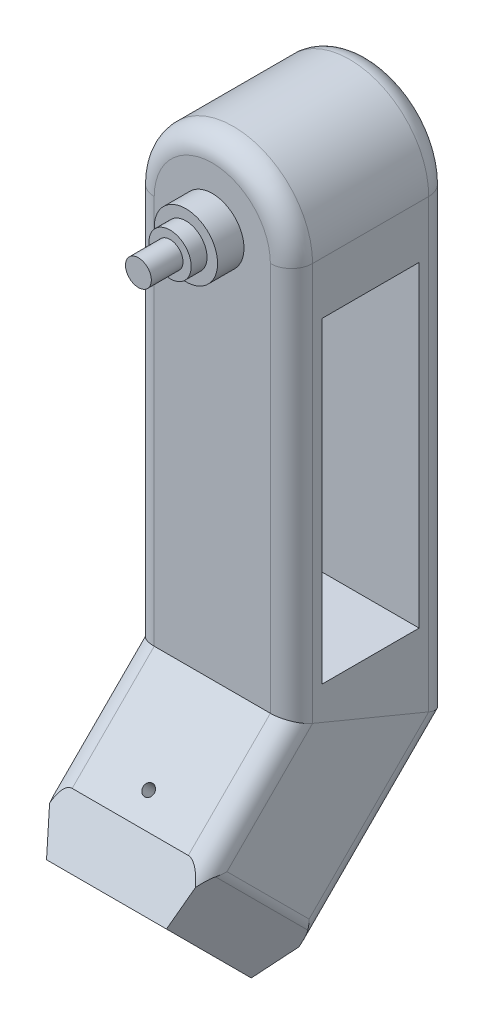
SolidWorks part; units mm, degrees
ref_plane "Front Plane" through (0, 0, 0) normal (0, 0, 1) x (1, 0, 0)
ref_plane "Top Plane" through (0, 0, 0) normal (0, 1, 0) x (1, 0, 0)
ref_plane "Right Plane" through (0, 0, 0) normal (1, 0, 0) x (0, 0, -1)
ref_plane "Plane2" through (0, 96.393, 0) normal (0, 1, 0) x (1, 0, 0)
sketch "Sketch10" plane through (0, 0, 0) normal (1, 0, 0) x (0, 0, -1)
  line L0 (0, 96.393) -> (0, -5.207)
  line L1 (55, 96.393) -> (-55, 96.393) construction
  line L2 (0, -5.207) -> (-25.3243, -30.5313)
  dimension "D1" = 101.6
  dimension "D2" = 35.814
  dimension "D3" = 135
sketch "Sketch11" plane through (0, 96.393, 0) normal (0, 1, 0) x (1, 0, 0)
  line L1 (-19.05, -19.05) -> (19.05, -19.05)
  line L2 (-19.05, -19.05) -> (-19.05, 19.05)
  line L3 (-19.05, 19.05) -> (19.05, 19.05)
  line L4 (19.05, -19.05) -> (19.05, 19.05)
  line L5 (-19.05, -19.05) -> (19.05, 19.05) construction
  line L6 (-19.05, 19.05) -> (19.05, -19.05) construction
  point P0 (0, 0)
  dimension "D1" = 38.1
sweep "Sweep1" add profiles "Sketch11" path "Sketch10"
sketch "Sketch12" plane through (0, -27.9278, 27.9278) normal (0, -0.7071, 0.7071) x (1, 0, 0)
  line L4 (19.05, -22.7319) -> (19.05, 15.3681)
  line L5 (19.05, -22.7319) -> (19.05, 15.3681)
  line L6 (19.05, 15.3681) -> (-19.05, 15.3681)
  line L7 (19.05, 15.3681) -> (-19.05, 15.3681)
  line L8 (-19.05, 15.3681) -> (-19.05, -22.7319)
  line L9 (-19.05, 15.3681) -> (-19.05, -22.7319)
  line L10 (-19.05, -22.7319) -> (19.05, -22.7319)
  line L11 (-19.05, -22.7319) -> (19.05, -22.7319)
  dimension "D1" = 0
extrude "Boss-Extrude5" add sketch "Sketch12" along normal blind 12.7 draft 20
sketch "Sketch13" plane through (0, 0, -19.05) normal (0, 0, -1) x (-1, 0, 0)
  line L0 (20.955, 96.393) -> (-20.955, 96.393) construction
  line L1 (0, 31.8146) -> (0, -31.8146) construction
  line L2 (-19.05, 96.393) -> (19.05, 96.393)
  arc A0 (19.05, 96.393) -> (-19.05, 96.393) centre (0, 96.393) ccw
  dimension "D1" = 38.1
extrude "Boss-Extrude6" add sketch "Sketch13" against normal up to surface (38.1 mm away) up to face at (0, 49.5384, 19.05)
sketch "Sketch15" plane through (0, -36.9081, 36.9081) normal (0, -0.7071, 0.7071) x (1, 0, 0)
  line L1 (-14.4276, 10.7457) -> (14.4276, -18.1095) construction
  line L2 (-14.4276, -18.1095) -> (14.4276, 10.7457) construction
  circle A2 centre (0, -3.6819) radius 12.065
  dimension "D1" = 24.13
extrude "Cut-Extrude3" cut sketch "Sketch15" against normal blind 25.4
sketch "Sketch16" plane through (19.05, 0, 0) normal (1, 0, 0) x (0, 0, -1)
  line L0 (0, 96.393) -> (0, 0) construction
  line L1 (-19.05, 96.393) -> (19.05, 96.393) construction
  line L2 (-19.05, 49.5384) -> (19.05, 49.5384) construction
  line L3 (-19.05, 96.393) -> (-19.05, 2.6838) construction
  line L4 (19.05, 96.393) -> (19.05, -13.0978) construction
  line L5 (-11.6553, 83.82) -> (11.6553, 83.82)
  line L6 (11.6553, 83.82) -> (11.6553, 7.62)
  line L7 (11.6553, 7.62) -> (-11.6553, 7.62)
  line L8 (-11.6553, 7.62) -> (-11.6553, 83.82)
  point P13 (0, 83.82)
  dimension "D1" = 90
  dimension "D2" = 90
  dimension "D3" = 90
  dimension "D4" = 90
  dimension "D5" = 76.2
  dimension "D6" = 23.3106
  dimension "D7" = 23.3106
  dimension "D8" = 83.82
extrude "Cut-Extrude4" cut sketch "Sketch16" against normal blind 59.8307
sketch "Sketch17" plane through (0, 0, 19.05) normal (0, 0, 1) x (1, 0, 0)
  line L0 (0, 115.443) -> (0, 96.393) construction
  line L1 (-19.05, 96.393) -> (19.05, 96.393) construction
  arc A0 (19.05, 96.393) -> (-19.05, 96.393) centre (0, 96.393) ccw construction
  circle A1 centre (0, 96.393) radius 7.62
  dimension "D1" = 15.24
extrude "Boss-Extrude7" add sketch "Sketch17" along normal blind 6.35
sketch "Sketch18" plane through (0, 0, 25.4) normal (0, 0, 1) x (1, 0, 0)
  circle A0 centre (0, 96.393) radius 5.08
  dimension "D1" = 10.16
extrude "Boss-Extrude8" add sketch "Sketch18" along normal blind 3.81
sketch "Sketch19" plane through (0, 0, 29.21) normal (0, 0, 1) x (1, 0, 0)
  circle A0 centre (0, 96.393) radius 3.1115
  dimension "D1" = 6.223
extrude "Boss-Extrude9" add sketch "Sketch19" along normal blind 7.62
fillet "Fillet2" radius 5.08 12 edges at (19.05, 41.6476, -19.05) (0, 115.443, -19.05) (19.05, 49.5384, 19.05) (0, 115.443, 19.05) (-19.05, -7.1886, 28.9224) (-19.05, -30.5313, 25.3243) (-19.05, -28.5497, -3.598) (-19.05, 41.6476, -19.05) (-19.05, 49.5384, 19.05) (19.05, -30.5313, 25.3243) (19.05, -28.5497, -3.598) (19.05, -7.1886, 28.9224)
sketch "Sketch21" plane through (0, -16.0739, -16.0739) normal (0, -0.7071, -0.7071) x (1, 0, 0)
  line L0 (-13.97, 39.4959) -> (13.97, 26.9753) construction
  line L1 (13.97, -4.2089) -> (13.97, 39.4959) construction
  line L2 (13.97, 26.9753) -> (-13.97, 26.9753) construction
  line L3 (-13.97, 39.4959) -> (-13.97, -4.2089) construction
  line L4 (13.97, 39.4959) -> (-13.97, 26.9753) construction
  circle A0 centre (0, 33.2356) radius 1.35
  dimension "D1" = 2.7
  dimension "D2" = 33.2356
extrude "Cut-Extrude5" cut sketch "Sketch21" against normal blind 63.349
